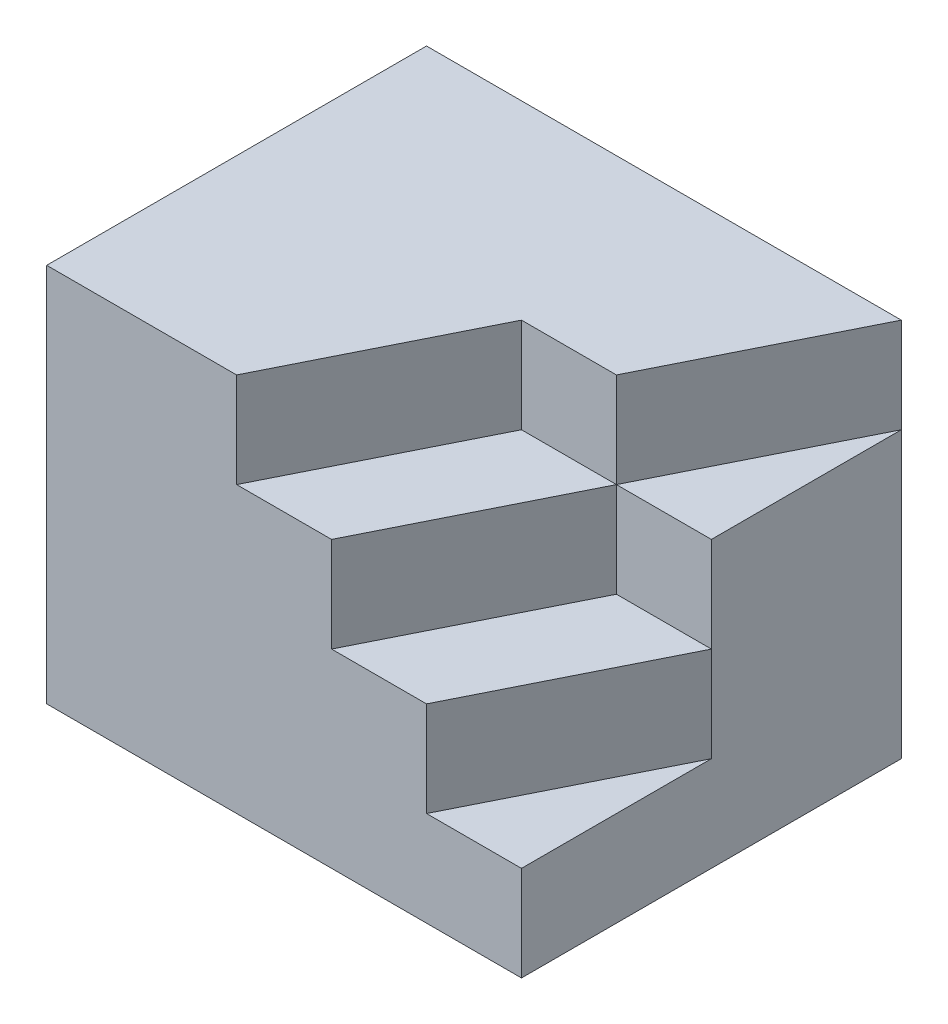
SolidWorks part; units mm, degrees
ref_plane "前基準面" through (0, 0, 0) normal (0, 0, 1) x (1, 0, 0)
ref_plane "上基準面" through (0, 0, 0) normal (0, 1, 0) x (1, 0, 0)
ref_plane "右基準面" through (0, 0, 0) normal (1, 0, 0) x (0, 0, -1)
sketch "草圖1" plane through (0, 0, 0) normal (0, 1, 0) x (1, 0, 0)
  line L0 (2.5, 0) -> (-2.5, -10)
  line L1 (12.5, 10) -> (-12.5, 10)
  line L2 (12.5, 10) -> (12.5, -10)
  line L3 (12.5, -10) -> (-12.5, -10)
  line L4 (-12.5, 10) -> (-12.5, -10)
  line L5 (12.5, 10) -> (-12.5, -10) construction
  line L6 (12.5, -10) -> (-12.5, 10) construction
  line L7 (-2.5, -10) -> (7.5, -10)
  line L8 (7.5, -10) -> (12.5, 0)
  line L9 (12.5, 0) -> (2.5, 0)
  line L10 (2.5, 0) -> (7.5, 0)
  line L11 (7.5, 0) -> (2.5, -10)
  line L12 (7.5, 0) -> (12.5, 10)
  point P0 (0, 0)
  dimension "D1" = 25
  dimension "D2" = 20
  dimension "D3" = 5
  dimension "D4" = 5
  dimension "D5" = 5
  dimension "D6" = 5
  dimension "D7" = 5
  dimension "D8" = 10
extrude "填料-伸長1" add sketch "草圖1" along normal blind 5 contours L8 L3 L2 | L9 L11 L3 L8 | L11 L9 L0 L7 | L9 L12 L1 L4 L3 L0 | L12 L9 L2 region at (2.5, 0, 5) region at (-2.9762, 0, -1.6667) region at (10.8333, 0, -3.3333) region at (7.5, 0, 5) region at (10.8333, 0, 6.6667)
extrude "填料-伸長2" add sketch "草圖1<3>" along normal blind 10 contours L9 L11 L3 L8 | L12 L9 L2 | L11 L9 L0 L7 | L9 L12 L1 L4 L3 L0 region at (2.5, 0, 5) region at (-2.9762, 0, -1.6667) region at (10.8333, 0, -3.3333) region at (7.5, 0, 5)
sketch "草圖1<3>" plane through (0, 0, 0) normal (0, 1, 0) x (1, 0, 0) same geometry as "草圖1"
extrude "填料-伸長4" add sketch "草圖1<5>" along normal blind 20 contours L9 L12 L1 L4 L3 L0 region at (-2.9762, 0, -1.6667)
sketch "草圖1<5>" plane through (0, 0, 0) normal (0, 1, 0) x (1, 0, 0) same geometry as "草圖1"
extrude "填料-伸長5" add sketch "草圖1<6>" along normal blind 15 contours L12 L9 L2 | L11 L9 L0 L7 region at (2.5, 0, 5) region at (10.8333, 0, -3.3333)
sketch "草圖1<6>" plane through (0, 0, 0) normal (0, 1, 0) x (1, 0, 0) same geometry as "草圖1"
